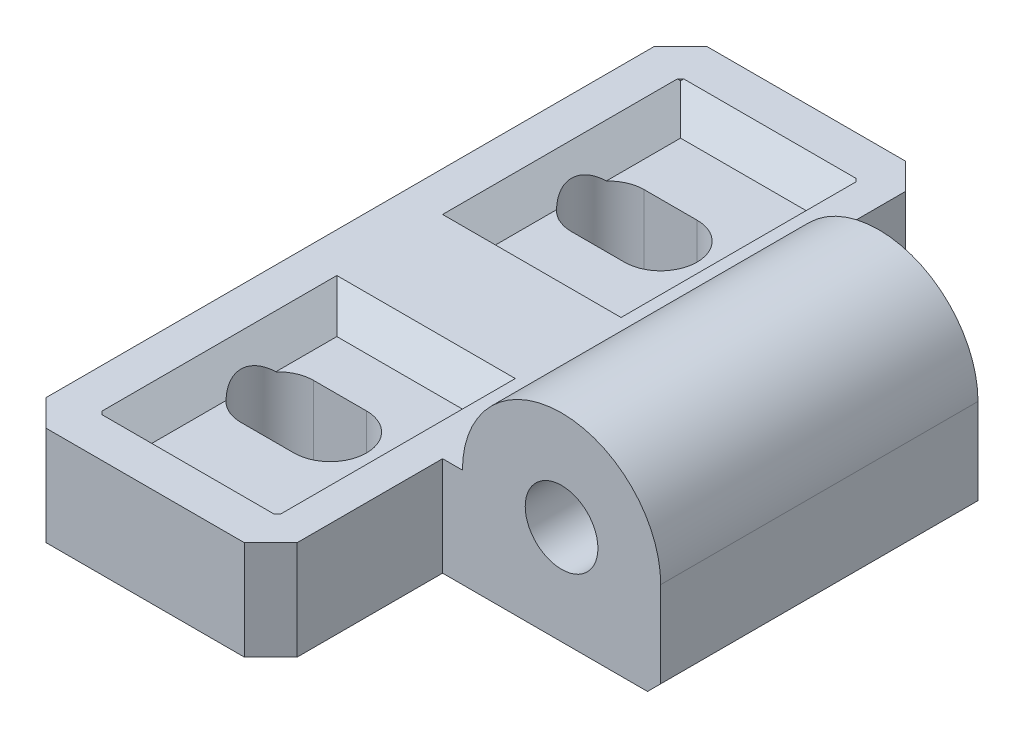
SolidWorks part; units mm, degrees
ref_plane "Front Plane" through (0, 0, 0) normal (0, 0, 1) x (1, 0, 0)
ref_plane "Top Plane" through (0, 0, 0) normal (0, 1, 0) x (1, 0, 0)
ref_plane "Right Plane" through (0, 0, 0) normal (1, 0, 0) x (0, 0, -1)
sketch "contour" plane through (0, 0, 0) normal (0, 0, 1) x (1, 0, 0)
  line L0 (0, -7.5) -> (6.5, -7.5)
  line L1 (-7.5, -0.0001) -> (-28, -0.0001)
  line L2 (7.5, -6.5) -> (7.5, 0)
  line L3 (0, -7.5) -> (-28, -7.5)
  line L4 (-28, -0.0001) -> (-28, -7.5)
  line L5 (6.5, -7.5) -> (7.5, -6.5)
  arc A0 (7.5, 0) -> (-7.5, -0.0001) centre (0, 0) ccw
  point P6 (7.5, -7.5)
  dimension "D2" = 15
  dimension "D1" = 7.4999
  dimension "D3" = 28
extrude "Boss-Extrude1" add sketch "contour" along normal mid plane 50
sketch "Sketch6" plane through (0, -7.5, 0) normal (0, -1, 0) x (1, 0, 0)
  line L0 (-28, 25) -> (-28, -25) construction
  line L1 (-28, 25) -> (6.5, 25) construction
  line L2 (-21, 12.5) -> (-17, 12.5) construction
  line L3 (-21, 15.25) -> (-17, 15.25)
  line L4 (-21, 9.75) -> (-17, 9.75)
  line L5 (-21, -12.5) -> (-17, -12.5) construction
  line L6 (-21, -9.75) -> (-17, -9.75)
  line L7 (-21, -15.25) -> (-17, -15.25)
  circle A0 centre (-19, 12.5) radius 2.75 construction
  circle A1 centre (-19, -12.5) radius 2.75 construction
  arc A2 (-21, 15.25) -> (-21, 9.75) centre (-21, 12.5) ccw
  arc A3 (-17, 9.75) -> (-17, 15.25) centre (-17, 12.5) ccw
  arc A4 (-21, -9.75) -> (-21, -15.25) centre (-21, -12.5) ccw
  arc A5 (-17, -15.25) -> (-17, -9.75) centre (-17, -12.5) ccw
  point P10 (-19, 12.5)
  point P17 (-19, -12.5)
  dimension "D1" = 5.5
  dimension "D2" = 9
  dimension "D5" = 4
  dimension "D3" = 12.5
  dimension "D4" = 25
extrude "mount-holes" cut sketch "Sketch6" against normal through all
sketch "Sketch7" plane through (0, -7.5, 0) normal (0, -1, 0) x (1, 0, 0)
  line L1 (-9, 12) -> (7.5, 12)
  line L2 (-9, 12) -> (-9, 25)
  line L3 (-9, 25) -> (7.5, 25)
  line L4 (7.5, 12) -> (7.5, 25)
  line L7 (-9, -12) -> (7.5, -12)
  line L8 (-9, -12) -> (-9, -25)
  line L9 (-9, -25) -> (7.5, -25)
  line L10 (7.5, -12) -> (7.5, -25)
  line L11 (7.5, 25) -> (7.5, -25) construction
  line L12 (-28, -25) -> (6.5, -25) construction
  line L13 (-28, 25) -> (6.5, 25) construction
  dimension "D3" = 16.5
extrude "cut-part" cut sketch "Sketch7" against normal blind 20
sketch "Sketch10" plane through (0, 0, 0) normal (0, 0, 1) x (1, 0, 0)
  circle A0 centre (0, 0) radius 2.75
  dimension "D1" = 5.5
extrude "Cut-Extrude3" cut sketch "Sketch10" against normal mid plane 50
chamfer "Chamfer1" distance 2 angle 45 4 edges at (-9, -3.75, -25) (-28, -3.75, -25) (-28, -3.75, 25) (-9, -3.75, 25)
sketch "Sketch11" plane through (0, -0.0001, 0) normal (0, 1, 0) x (1, 0, 0)
  line L0 (-25, 0) -> (-11.5, 0) construction
  line L1 (-25, -4) -> (-11.5, -4)
  line L2 (-25, 4) -> (-11.5, 4)
  line L3 (-25, -4) -> (-25, -21.7574)
  line L4 (-11.5, 4) -> (-11.5, 21.7574)
  line L36 (-11.5, -21.7574) -> (-11.5, -4)
  line L37 (-11.5, 21.7574) -> (-11.7426, 22)
  line L38 (-11.7426, 22) -> (-24.7574, 22)
  line L39 (-24.7574, 22) -> (-25, 21.7574)
  line L40 (-25, 21.7574) -> (-25, 4)
  line L41 (-25, -21.7574) -> (-24.7574, -22)
  line L42 (-24.7574, -22) -> (-11.7426, -22)
  line L43 (-11.7426, -22) -> (-11.5, -21.7574)
  dimension "D1" = 4
  dimension "D2" = 4
extrude "Cut-Extrude4" cut sketch "Sketch11" against normal blind 2
chamfer "Chamfer2" distance 2 angle 45 8 edges at (-11.5, -2.0001, 12.8787) (-18.25, -2.0001, 22) (-25, -2.0001, -12.8787) (-18.25, -2.0001, -22) (-11.5, -2.0001, -12.8787) (-18.25, -2.0001, -4) (-18.25, -2.0001, 4) (-25, -2.0001, 12.8787)
